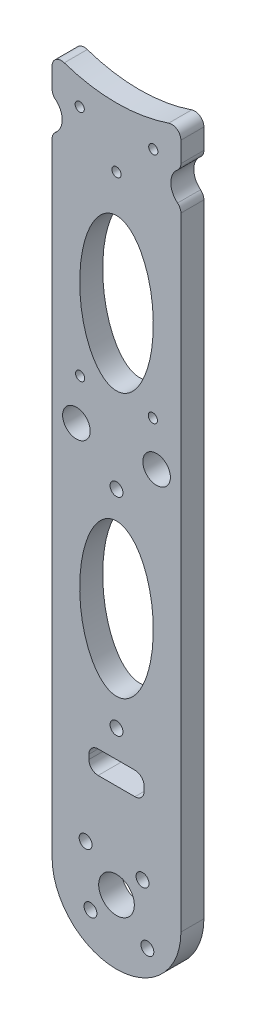
SolidWorks part; units mm, degrees
ref_plane "Front Plane" through (0, 0, 0) normal (0, 0, 1) x (1, 0, 0)
ref_plane "Top Plane" through (0, 0, 0) normal (0, 1, 0) x (1, 0, 0)
ref_plane "Right Plane" through (0, 0, 0) normal (1, 0, 0) x (0, 0, -1)
sketch "Sketch1" plane through (0, 0, 0) normal (0, 0, 1) x (1, 0, 0)
  line L0 (-14, 0) -> (-14, 135.3474)
  line L1 (0, 149.0732) -> (0, -14) construction
  line L2 (14, 0) -> (14, 135.3474)
  line L3 (-14, 0) -> (14, 0) construction
  line L4 (-6.7175, 6.7175) -> (6.7175, -6.7175) construction
  line L6 (-9.9779, -9.9779) -> (8.2462, 8.2462) construction
  line L7 (-14, 144.6611) -> (-14, 149.0732)
  line L8 (-4, 20.4839) -> (4, 20.4839)
  line L9 (-6, 22.4839) -> (-6, 23.4839)
  line L10 (-4, 25.4839) -> (4, 25.4839)
  line L11 (6, 22.4839) -> (6, 23.4839)
  line L12 (-6, 20.4839) -> (6, 25.4839) construction
  line L13 (-6, 25.4839) -> (6, 20.4839) construction
  line L14 (14, 144.6611) -> (14, 149.0732)
  arc A0 (-14, 0) -> (14, 0) centre (0, 0) ccw
  arc A1 (-11.3514, 150.9651) -> (11.3514, 150.9651) centre (0, 184.0732) ccw
  circle A2 centre (-8, 144.3712) radius 1
  circle A3 centre (6.7175, -6.7175) radius 1.4
  circle A4 centre (-5.6569, -5.6569) radius 1.4
  circle A5 centre (5.6569, 5.6569) radius 1.4
  circle A6 centre (-6.7175, 6.7175) radius 1.4
  circle A7 centre (8, 144.3712) radius 1
  circle A8 centre (0, 136.0732) radius 1
  circle A9 centre (0, 136.0732) radius 1 construction
  circle A10 centre (-8, 144.3712) radius 1 construction
  circle A11 centre (8, 144.3712) radius 1 construction
  circle A12 centre (7.9033, 93.7383) radius 1
  circle A13 centre (0, 184.0732) radius 35 construction
  circle A16 centre (7.9033, 93.7383) radius 1 construction
  circle A17 centre (0, 31.3839) radius 1.4
  circle A18 centre (0, 76.3839) radius 1.4
  circle A20 centre (8.7156, 84.4537) radius 3
  circle A21 centre (8.7156, 84.4537) radius 1.45 construction
  arc A22 (6, 22.4839) -> (4, 20.4839) centre (4, 22.4839) cw
  arc A23 (4, 25.4839) -> (6, 23.4839) centre (4, 23.4839) cw
  arc A24 (-4, 25.4839) -> (-6, 23.4839) centre (-4, 23.4839) ccw
  arc A25 (-6, 22.4839) -> (-4, 20.4839) centre (-4, 22.4839) ccw
  arc A26 (-14, 149.0732) -> (-11.3514, 150.9651) centre (-12, 149.0732) cw
  arc A27 (11.3514, 150.9651) -> (14, 149.0732) centre (12, 149.0732) cw
  arc A28 (-13.2731, 143.1186) -> (-13.2731, 136.8899) centre (-15.8435, 140.0042) cw
  arc A29 (13.2731, 143.1186) -> (13.2731, 136.8899) centre (15.8435, 140.0042) ccw
  arc A30 (14, 135.3474) -> (13.2731, 136.8899) centre (12, 135.3474) ccw
  arc A31 (13.2731, 143.1186) -> (14, 144.6611) centre (12, 144.6611) ccw
  arc A32 (-14, 144.6611) -> (-13.2731, 143.1186) centre (-12, 144.6611) ccw
  arc A33 (-13.2731, 136.8899) -> (-14, 135.3474) centre (-12, 135.3474) ccw
  circle A34 centre (-7.9033, 93.7383) radius 1
  circle A35 centre (-8.7156, 84.4537) radius 3
  ellipse E0 centre (0, 53.8839) end of major axis (0, 70.3839) minor radius 8
  ellipse E1 centre (0, 111.3839) end of major axis (0, 127.8839) minor radius 8
  point P43 (0, 22.9839)
  point P82 (-14, 151.9952)
  point P85 (14, 151.9952)
  point P94 (14, 136.4115)
  point P97 (14, 143.597)
  point P100 (-14, 143.597)
  point P103 (-14, 136.4115)
  dimension "D3" = 14
  dimension "D5" = 2
  dimension "D2" = 2
  dimension "D4" = 12
  dimension "D8" = 35
  dimension "D10" = 22.5
  dimension "D11" = 9.5
  dimension "D7" = 2.8
  dimension "D15" = 2
  dimension "D16" = 2
  dimension "D18" = 2.8
  dimension "D19" = 9.5
  dimension "D20" = 8
  dimension "D6" = 5
  dimension "D9" = 45
  dimension "D12" = 8
  dimension "D13" = 8
  dimension "D14" = 35
  dimension "D17" = 8
  dimension "D21" = 8.4
  dimension "D22" = 163.0732
extrude "Boss-Extrude1" add sketch "Sketch1" along normal blind 5
sketch "Sketch2" plane through (0, 0, 5) normal (0, 0, 1) x (1, 0, 0)
  circle A0 centre (0, 0) radius 3.875
extrude "Cut-Extrude1" cut sketch "Sketch2" against normal up to next
